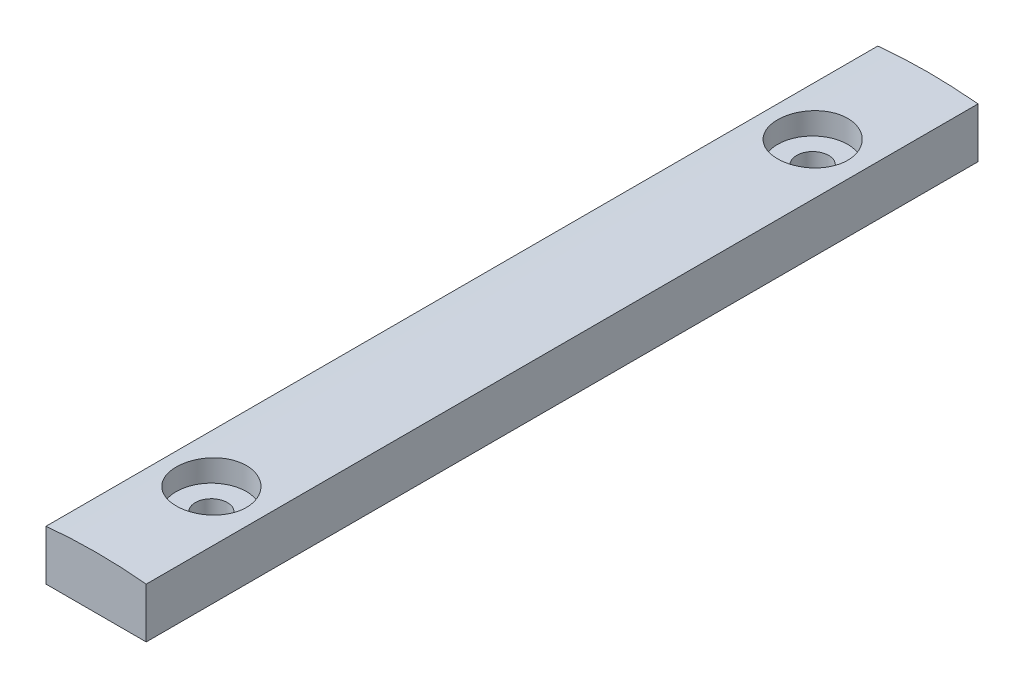
SolidWorks part; units mm, degrees
ref_plane "前视基准面" through (0, 0, 0) normal (0, 0, 1) x (1, 0, 0)
ref_plane "上视基准面" through (0, 0, 0) normal (0, 1, 0) x (1, 0, 0)
ref_plane "右视基准面" through (0, 0, 0) normal (1, 0, 0) x (0, 0, -1)
sketch "草图1" plane through (0, 0, 0) normal (0, 0, 1) x (1, 0, 0)
  line L1 (0, 0) -> (10, 0)
  line L2 (0, 0) -> (0, 5)
  line L4 (10, 0) -> (10, 5)
  arc A0 (0, 5) -> (10, 5) centre (5, -44.7494) cw
extrude "凸台-拉伸1" add sketch "草图1" along normal blind 83
ref_plane "基准面1" through (0, 5, 0) normal (0, 1, 0) x (1, 0, 0)
sketch "草图5" plane through (0, 5, 0) normal (0, 1, 0) x (1, 0, 0)
  circle A0 centre (5, -71.5) radius 3.5
sketch "草图6" plane through (0, 5, 0) normal (0, 1, 0) x (1, 0, 0)
  circle A0 centre (5, -71.5) radius 1.6
extrude "切除-拉伸1" cut sketch "草图6" against normal blind 10 and the other way blind 5
extrude "切除-拉伸2" cut sketch "草图5" against normal blind 2 and the other way blind 2 contours A0
ref_plane "基准面2" through (0, 0, 41.5) normal (0, 0, -1) x (-1, 0, 0)
mirror "镜向1" about plane through (0, 0, 41.5) normal (0, 0, -1) of "切除-拉伸2", "切除-拉伸1"
